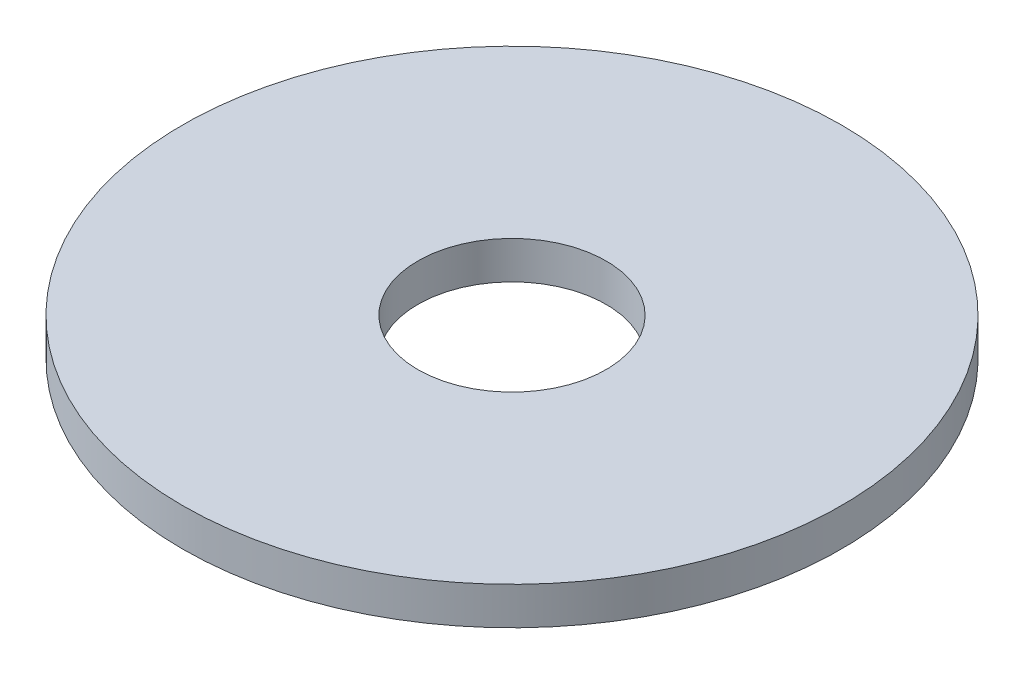
SolidWorks part; units mm, degrees
ref_plane "Front Plane" through (0, 0, 0) normal (0, 0, 1) x (1, 0, 0)
ref_plane "Top Plane" through (0, 0, 0) normal (0, 1, 0) x (1, 0, 0)
ref_plane "Right Plane" through (0, 0, 0) normal (1, 0, 0) x (0, 0, -1)
sketch "Sketch1" plane through (0, 0, 0) normal (0, 1, 0) x (1, 0, 0)
  circle A0 centre (0, 0) radius 52.5
  dimension "FLANGE_OD" = 105
extrude "Boss-Extrude1" add sketch "Sketch1" along normal blind 6
sketch "Sketch2" plane through (0, 0, 0) normal (0, 1, 0) x (1, 0, 0)
  circle A0 centre (0, 0) radius 15
  dimension "BORE_D" = 30
extrude "Cut-Extrude1" cut sketch "Sketch2" along normal through all
sketch "Sketch3" plane through (0, 6, 0) normal (0, 1, 0) x (1, 0, 0)
  circle A0 centre (0, 0) radius 9.7126 construction
  circle A1 centre (-9.7126, 0) radius 2.2352
  dimension "BOLT_D" = 4.4703
  dimension "BOLT_PCD" = 19.4253
extrude "Cut-Extrude2" cut sketch "Sketch3" against normal blind 5.9921 rebuild error yes
pattern_circular "CirPattern1" count 8 over 360 rebuild error yes
